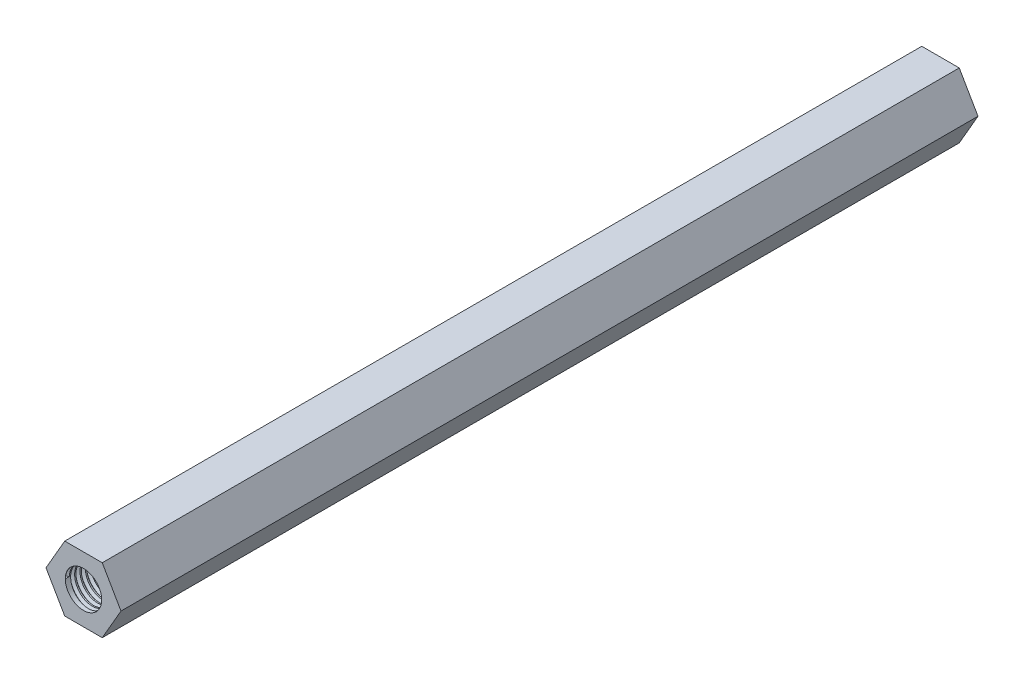
SolidWorks part; units mm, degrees
material "1.7036 (28CrS4)"
ref_plane "Plan de face" through (0, 0, 0) normal (0, 0, 1) x (1, 0, 0)
ref_plane "Plan de dessus" through (0, 0, 0) normal (0, 1, 0) x (1, 0, 0)
ref_plane "Plan de droite" through (0, 0, 0) normal (1, 0, 0) x (0, 0, -1)
sketch "Esquisse1" plane through (0, 0, 0) normal (0, 0, 1) x (1, 0, 0)
  line L0 (0, 3.5) -> (7, 3.5) construction
  line L1 (0, 0) -> (7, 0) construction
  line L2 (0, 0) -> (0, 7) construction
  line L3 (0, 7) -> (7, 7) construction
  line L4 (7, 0) -> (7, 7) construction
  line L5 (3.5, 7) -> (3.5, 0) construction
  line L7 (5.25, 0.4689) -> (7, 3.5)
  line L8 (7, 3.5) -> (5.25, 6.5311)
  line L9 (5.25, 6.5311) -> (1.75, 6.5311)
  line L10 (1.75, 6.5311) -> (0, 3.5)
  line L11 (0, 3.5) -> (1.75, 0.4689)
  line L12 (1.75, 0.4689) -> (5.25, 0.4689)
  circle A0 centre (3.5, 3.5) radius 3.5 construction
  dimension "D3" = 7
  dimension "D1" = 7
  dimension "D2" = 7
extrude "Boss.-Extru.1" add sketch "Esquisse1" along normal blind 80
sketch "Esquisse2" plane through (0, 0, 80) normal (0, 0, 1) x (1, 0, 0)
  line L0 (3.5, 6.5311) -> (3.5, 0.4689) construction
  line L1 (0.875, 1.9845) -> (6.125, 5.0155) construction
  line L6 (1.75, 0.4689) -> (5.25, 0.4689)
  line L7 (5.25, 0.4689) -> (7, 3.5)
  line L8 (7, 3.5) -> (5.25, 6.5311)
  line L9 (5.25, 6.5311) -> (1.75, 6.5311)
  line L10 (1.75, 6.5311) -> (0, 3.5)
  line L11 (0, 3.5) -> (1.75, 0.4689)
  line L12 (1.75, 0.4689) -> (5.25, 0.4689)
  line L13 (5.25, 0.4689) -> (7, 3.5)
  line L14 (7, 3.5) -> (5.25, 6.5311)
  line L15 (5.25, 6.5311) -> (1.75, 6.5311)
  line L16 (1.75, 6.5311) -> (0, 3.5)
  line L17 (0, 3.5) -> (1.75, 0.4689)
  circle A0 centre (3.5, 3.5) radius 1.5
  dimension "D2" = 3
  dimension "D1" = 0
hole_wizard "Dégagement M31" positions "Esquisse6" profile "Esquisse7" hole size "M3" standard "ISO"
sketch "Esquisse6" plane through (0, 0, 80) normal (0, 0, 1) x (1, 0, 0)
  point P0 (3.5, 3.5)
sketch "Esquisse7" plane through (3.5, 3.5, 80) normal (1, 0, 0) x (0, -1, 0)
  line L0 (0, 0) -> (0, 16.0215)
  line L1 (0, 16.0215) -> (1.7, 15)
  line L2 (1.7, 15) -> (1.7, 0)
  line L5 (1.7, 0) -> (0, 0)
  line L10 (0, 16.0215) -> (-1.7, 15) construction
  line L11 (0, -6.35) -> (0, 107.95) construction
  dimension "Diamètre du perçage" = 3.4
  dimension "Profondeur du perçage" = 15
  dimension "Angle de pointe" = 118
thread "Filetage1" pitch 0.5 method cut profile "Profil de filetage1" start angle 0, offset 0, length 15, pitch 0.5, diameter 3.4
ref_plane "Plan1" through (1.8, 3.5, 80) normal (0, -1, 0) x (-1, 0, 0)
sketch "Profil de filetage1" plane through (1.8, 3.5, 80) normal (0, -1, 0) x (-1, 0, 0)
  line L0 (0, 0) -> (0, 0.5) construction
  line L1 (0, 0) -> (0.2706, 0.1562)
  line L2 (0.2706, 0.1562) -> (0.2706, 0.2187)
  line L3 (0.2706, 0.2187) -> (0, 0.375)
  line L4 (0.2706, 0.1875) -> (0, 0.1875) construction
  line L11 (0, 0) -> (0, 0.375)
  point P2 (0, 0)
  dimension "Pitch" = 0.5
  dimension "Profile_Angle" = 60
  dimension "Profile_Land" = 0.0625
  dimension "Profile_Height" = 0.2706
hole_wizard "Dégagement M32" positions "Esquisse10" profile "Esquisse11" hole size "M3" standard "ISO"
sketch "Esquisse10" plane through (0, 0, 0) normal (0, 0, -1) x (-1, 0, 0)
  point P0 (-3.5, 3.5)
sketch "Esquisse11" plane through (3.5, 3.5, 0) normal (1, 0, 0) x (0, 1, 0)
  line L0 (0, 0) -> (0, 9.0215)
  line L1 (0, 9.0215) -> (1.7, 8)
  line L2 (1.7, 8) -> (1.7, 0)
  line L5 (1.7, 0) -> (0, 0)
  line L10 (0, 9.0215) -> (-1.7, 8) construction
  line L11 (0, -6.35) -> (0, 107.95) construction
  dimension "Diamètre du perçage" = 3.4
  dimension "Profondeur du perçage" = 8
  dimension "Angle de pointe" = 118
sketch "Esquisse12" plane through (0, 0, 0) normal (0, 0, -1) x (-1, 0, 0)
  line L6 (-5.25, 0.4689) -> (-1.75, 0.4689)
  line L7 (-1.75, 0.4689) -> (0, 3.5)
  line L8 (0, 3.5) -> (-1.75, 6.5311)
  line L9 (-1.75, 6.5311) -> (-5.25, 6.5311)
  line L10 (-5.25, 6.5311) -> (-7, 3.5)
  line L11 (-7, 3.5) -> (-5.25, 0.4689)
  line L12 (-5.25, 0.4689) -> (-1.75, 0.4689)
  line L13 (-1.75, 0.4689) -> (0, 3.5)
  line L14 (0, 3.5) -> (-1.75, 6.5311)
  line L15 (-1.75, 6.5311) -> (-5.25, 6.5311)
  line L16 (-5.25, 6.5311) -> (-7, 3.5)
  line L17 (-7, 3.5) -> (-5.25, 0.4689)
  circle A0 centre (-3.5, 3.5) radius 1.5
  dimension "D2" = 3
  dimension "D1" = 0
extrude "Enlèv. mat.-Extru.1" [suppressed] cut sketch "Esquisse12" against normal blind 15
thread "Filetage2" pitch 0.5 method cut profile "Profil de filetage2" start angle 0, offset 0, length 10, pitch 0.5, diameter 3.4
ref_plane "Plan2" through (5.2, 3.5, 0) normal (0, -1, 0) x (1, 0, 0)
sketch "Profil de filetage2" plane through (5.2, 3.5, 0) normal (0, -1, 0) x (1, 0, 0)
  line L0 (0, 0) -> (0, 0.5) construction
  line L1 (0, 0) -> (0.2706, 0.1562)
  line L2 (0.2706, 0.1562) -> (0.2706, 0.2187)
  line L3 (0.2706, 0.2187) -> (0, 0.375)
  line L4 (0.2706, 0.1875) -> (0, 0.1875) construction
  line L11 (0, 0) -> (0, 0.375)
  point P2 (0, 0)
  dimension "Pitch" = 0.5
  dimension "Profile_Angle" = 60
  dimension "Profile_Land" = 0.0625
  dimension "Profile_Height" = 0.2706
equation "\"diam_cercle_circons\"= 7"
equation "\"D1@Esquisse1\"=\"diam_cercle_circons\""
equation "\"D2@Esquisse1\"=\"diam_cercle_circons\""
equation "\"Hauteur\"=80"
equation "\"D1@Boss.-Extru.1\"=\"Hauteur\""
equation "\"D3@Esquisse1\"=\"diam_cercle_circons\""
